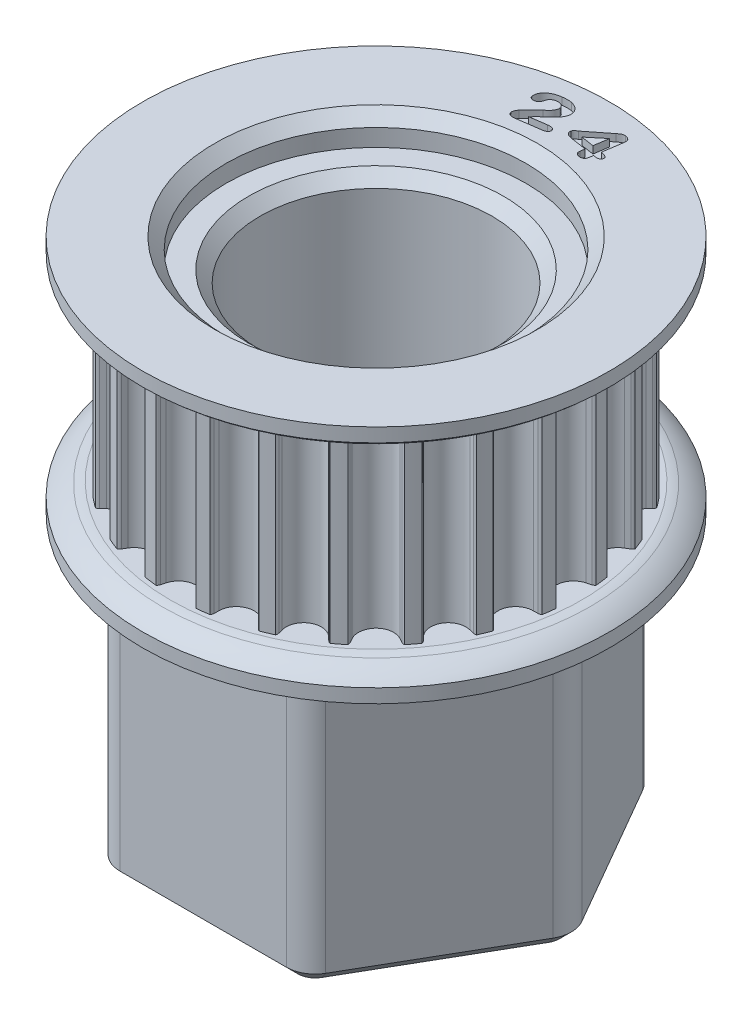
SolidWorks part; units mm, degrees
other "DetailItem2"
material "Markforged"
ref_plane "Front Plane" through (0, 0, 0) normal (0, 0, 1) x (1, 0, 0)
ref_plane "Top Plane" through (0, 0, 0) normal (0, 1, 0) x (1, 0, 0)
ref_plane "Right Plane" through (0, 0, 0) normal (1, 0, 0) x (0, 0, -1)
ref_axis "Centerline" through (0, 8.7312, 0) along (0, -1, 0)
sketch "Sketch1" plane through (0, 0, 0) normal (0, 1, 0) x (1, 0, 0)
  circle A0 centre (0, 0) radius 11.0782
  dimension "OuterDiameter" = 22.1563
extrude "ToothOD" add sketch "Sketch1" along normal mid plane 10.16
sketch "Sketch2" plane through (0, 0, 0) normal (0, 1, 0) x (1, 0, 0)
  line L0 (0, 9.9098) -> (50000, 9.9098) construction
  line L1 (0, 11.0782) -> (50000, 11.0782) construction
  line L2 (0, 0) -> (0, 50000) construction
  arc A0 (-0.937, 10.6282) -> (0, 9.9098) centre (0, 10.88) ccw
  arc A1 (-1.1005, 11.0234) -> (1.1005, 11.0234) centre (0, 0) cw
  circle A2 centre (0, 0) radius 11.0782 construction
  arc A3 (-0.937, 10.6282) -> (-1.0078, 10.88) centre (-11.9754, 7.6618) ccw
  arc A4 (-1.0078, 10.88) -> (-1.1005, 11.0234) centre (-1.2954, 10.7956) ccw
  circle A5 centre (0, 0) radius 11.0782 construction
  arc A6 (0.937, 10.6282) -> (1.0078, 10.88) centre (11.9754, 7.6618) cw
  arc A7 (1.0078, 10.88) -> (1.1005, 11.0234) centre (1.2954, 10.7956) cw
  arc A8 (0, 9.9098) -> (0.937, 10.6282) centre (0, 10.88) ccw
  dimension "D1" = 1.9406
  dimension "D3" = 22.86
  dimension "D4" = 0.5994
  dimension "D2" = 1.1684
  dimension "D5" = 1.2954
extrude "ToothProfile" cut sketch "Sketch2" against normal through all both and the other way through all
pattern_circular "ToothPattern" count 24 over 360 about axis through (0, 5.08, 0) along (0, -1, 0) of "ToothProfile"
sketch "Sketch4" plane through (0, 0, 0) normal (0, 0, 1) x (1, 0, 0)
  line L0 (0, -5.08) -> (11.3322, -5.08)
  line L1 (0, -6.604) -> (12.8562, -6.604)
  line L2 (0, -6.604) -> (0, -5.08)
  line L3 (12.8562, -6.604) -> (12.8562, -5.842)
  line L4 (0, 0) -> (50000, 0) construction
  line L5 (12.8562, 6.604) -> (12.8562, 5.842)
  line L6 (0, 6.604) -> (0, 5.08)
  line L7 (0, 6.604) -> (12.8562, 6.604)
  line L8 (0, 5.08) -> (11.3322, 5.08)
  arc A0 (11.3322, -5.08) -> (11.7872, -5.1726) centre (11.0525, -7.618) cw
  arc A2 (11.7872, -5.1726) -> (12.8562, -5.842) centre (10.6547, -8.1694) cw
  arc A3 (11.7872, 5.1726) -> (12.8562, 5.842) centre (10.6547, 8.1694) ccw
  arc A4 (11.3322, 5.08) -> (11.7872, 5.1726) centre (11.0525, 7.618) ccw
  dimension "D5" = 2.5534
  dimension "D6" = 3.2036
  dimension "FlangeID" = 11.3322
  dimension "FlangeOD" = 12.8562
  dimension "D1" = 1.524
  dimension "D2" = 0.762
  dimension "D3" = 5.08
  dimension "D4" = 13.208
  dimension "D7" = 0.762
  dimension "D8" = 0.6694
  dimension "D10" = 1.0689
revolve "Flange" add sketch "Sketch4" angle 360 about axis through (0, 8.7312, 0) along (0, -1, 0)
sketch "Sketch6" plane through (0, 0, 0) normal (0, 0, 1) x (1, 0, 0)
  line L0 (0, -6.604) -> (0, -7.9375) construction
  line L1 (-12.8562, -6.604) -> (12.8562, -6.604) construction
  line L2 (0, -7.9375) -> (8.2931, -7.9375) construction
  line L3 (8.2931, -7.9375) -> (8.2931, -6.604) construction
  line L4 (8.2931, -6.604) -> (0, -6.604) construction
  line L5 (0, 0) -> (50000, 0) construction
  line L6 (8.2931, 6.604) -> (0, 6.604)
  line L7 (8.2931, 7.9375) -> (8.2931, 6.604)
  line L8 (0, 7.9375) -> (8.2931, 7.9375)
  line L9 (0, 6.604) -> (0, 7.9375)
  line L11 (36.0254, 12.0878) -> (29.4657, 15.4613) construction
  line L12 (29.4657, 15.4613) -> (23.2643, 11.4672) construction
  line L13 (23.2643, 11.4672) -> (23.6226, 4.0996) construction
  line L14 (23.6226, 4.0996) -> (30.1823, 0.7261) construction
  line L15 (30.1823, 0.7261) -> (36.3837, 4.7202) construction
  line L16 (36.3837, 4.7202) -> (36.0254, 12.0878) construction
  circle A0 centre (29.824, 8.0937) radius 6.3881 construction
  circle A1 centre (29.824, 8.0937) radius 8.2931 construction
  dimension "D2" = 12.7762
  dimension "D1" = 15.875
  dimension "D4" = 8.2931
  dimension "D3" = 1.905
  dimension "D5" = 1.3335
revolve "TopBearingBoss" [suppressed] add sketch "Sketch6" angle 360 about axis through (0, 8.7312, 0) along (0, -1, 0)
mirror "BottomBearingBoss" [suppressed] about plane through (0, 0, 0) normal (0, 1, 0)
sketch "Sketch7" plane through (0, 0, 0) normal (0, -1, 0) x (1, 0, 0)
  line L1 (3.6882, 6.3881) -> (-3.6882, 6.3881) construction
  line L2 (-3.6882, 6.3881) -> (-7.3763, 0) construction
  line L3 (-7.3763, 0) -> (-3.6882, -6.3881) construction
  line L4 (-3.6882, -6.3881) -> (3.6882, -6.3881) construction
  line L5 (3.6882, -6.3881) -> (7.3763, 0) construction
  line L6 (7.3763, 0) -> (3.6882, 6.3881) construction
  circle A0 centre (0, 0) radius 6.3881
  dimension "HexBoreDi," = 12.7762
extrude "Bore" cut sketch "Sketch7" against normal through all both and the other way through all
sketch "Sketch9" plane through (0, 6.604, 0) normal (0, 1, 0) x (1, 0, 0)
  arc A0 (-6.4927, -6.4927) -> (6.4927, -6.4927) centre (0, 0) cw construction
  text T0 "24" font "Arial Rounded MT Bold" height 4.572
  point P3 (0, 9.1821)
  dimension "D1" = 9.1821
  dimension "D2" = 270
extrude "Large Tooth Count" [suppressed] cut sketch "Sketch9" against normal blind 0.4 and the other way through all
sketch "Sketch11" plane through (0, 6.604, 0) normal (0, 1, 0) x (1, 0, 0)
  arc A0 (-6.8456, -6.8456) -> (6.8456, -6.8456) centre (0, 0) cw construction
  circle A1 centre (0, 0) radius 12.8562 construction
  text T0 "<b>24</b>" font "Arial Rounded MT Bold" height 2.286
  point P6 (0, 9.6812)
  dimension "D1" = 3.175
  dimension "D3" = 270
extrude "Small Tooth Count" cut sketch "Sketch11" against normal blind 0.4 and the other way through all
sketch "Sketch12" plane through (0, -6.604, 0) normal (0, -1, 0) x (1, 0, 0)
  line L1 (5.4993, -9.525) -> (10.9985, 0)
  line L2 (10.9985, 0) -> (5.4993, 9.525)
  line L3 (5.4993, 9.525) -> (-5.4993, 9.525)
  line L4 (-5.4993, 9.525) -> (-10.9985, 0)
  line L5 (-10.9985, 0) -> (-5.4993, -9.525)
  line L6 (-5.4993, -9.525) -> (5.4993, -9.525)
  circle A0 centre (0, 0) radius 6.3881 construction
  circle A1 centre (0, 0) radius 6.3881
  circle A2 centre (0, 0) radius 9.525 construction
  dimension "D1" = 19.05
extrude "Boss-Extrude1" add sketch "Sketch12" along normal blind 15.24
sketch "Sketch27" plane through (0, 6.604, 0) normal (0, 1, 0) x (1, 0, 0)
  circle A0 centre (0, 0) radius 8.255
  dimension "D1" = 16.51
extrude "Cut-Extrude1" cut sketch "Sketch27" against normal blind 1.5875
fillet "Fillet1" radius 1.5875 6 edges at (-5.4993, -14.224, 9.525) (5.4993, -14.224, 9.525) (10.9985, -14.224, 0) (5.4993, -14.224, -9.525) (-10.9985, -14.224, 0) (-5.4993, -14.224, -9.525)
sketch "Sketch25" plane through (0, -6.604, 0) normal (0, -1, 0) x (1, 0, 0)
  line L6 (-4.5827, -9.525) -> (4.5827, -9.525)
  line L7 (-10.5403, -0.7937) -> (-5.9575, -8.7313)
  line L8 (-5.9575, 8.7312) -> (-10.5403, 0.7938)
  line L9 (4.5827, 9.525) -> (-4.5827, 9.525)
  line L10 (10.5403, 0.7938) -> (5.9575, 8.7312)
  line L11 (5.9575, -8.7312) -> (10.5403, -0.7937)
  line L12 (-4.5827, -9.525) -> (4.5827, -9.525)
  line L13 (-10.5403, -0.7937) -> (-5.9575, -8.7313)
  line L14 (-5.9575, 8.7312) -> (-10.5403, 0.7938)
  line L15 (4.5827, 9.525) -> (-4.5827, 9.525)
  line L16 (10.5403, 0.7938) -> (5.9575, 8.7312)
  line L17 (5.9575, -8.7312) -> (10.5403, -0.7937)
  arc A6 (-5.9575, -8.7313) -> (-4.5827, -9.525) centre (-4.5827, -7.9375) ccw
  arc A7 (-10.5403, 0.7938) -> (-10.5403, -0.7937) centre (-9.1654, 0) ccw
  arc A8 (-4.5827, 9.525) -> (-5.9575, 8.7312) centre (-4.5827, 7.9375) ccw
  arc A9 (5.9575, 8.7312) -> (4.5827, 9.525) centre (4.5827, 7.9375) ccw
  arc A10 (10.5403, -0.7937) -> (10.5403, 0.7938) centre (9.1654, 0) ccw
  arc A11 (4.5827, -9.525) -> (5.9575, -8.7312) centre (4.5827, -7.9375) ccw
  arc A12 (-5.9575, -8.7313) -> (-4.5827, -9.525) centre (-4.5827, -7.9375) ccw
  arc A13 (-10.5403, 0.7938) -> (-10.5403, -0.7937) centre (-9.1654, 0) ccw
  arc A14 (-4.5827, 9.525) -> (-5.9575, 8.7312) centre (-4.5827, 7.9375) ccw
  arc A15 (5.9575, 8.7312) -> (4.5827, 9.525) centre (4.5827, 7.9375) ccw
  arc A16 (10.5403, -0.7937) -> (10.5403, 0.7938) centre (9.1654, 0) ccw
  arc A17 (4.5827, -9.525) -> (5.9575, -8.7312) centre (4.5827, -7.9375) ccw
  dimension "D1" = 0
sweep "Cut-Sweep1" cut path "Sketch25" circular profile diameter 0.635 parameters "D3"=0.635
fillet "Fillet2" radius 1.27 24 edges at (-5.5352, -6.604, 9.5873) (0, -6.604, 9.8425) (5.5352, -6.604, 9.5873) (8.5239, -6.604, 4.9213) (11.0704, -6.604, 0) (8.5239, -6.604, -4.9212) (5.5352, -6.604, -9.5873) (0, -6.604, -9.8425) (-5.5352, -6.604, -9.5873) (-8.5239, -6.604, -4.9213) (-11.0704, -6.604, 0) (-10.7529, -6.9215, 0) (-8.2489, -6.9215, -4.7625) (-5.3765, -6.9215, -9.3123) (0, -6.9215, -9.525) (5.3765, -6.9215, -9.3123) (8.2489, -6.9215, -4.7625) (10.7529, -6.9215, 0) (8.2489, -6.9215, 4.7625) (5.3765, -6.9215, 9.3123) (0, -6.9215, 9.525) (-5.3765, -6.9215, 9.3123) (-8.5239, -6.604, 4.9212) (-8.2489, -6.9215, 4.7625)
chamfer "Chamfer1" distance 0.635 angle 45 3 edges at (0, -21.844, -6.3881) (0, 6.604, 8.255) (0, 5.0165, 6.3881)
chamfer "Chamfer2" distance 0.635 angle 45 12 edges at (0, -21.844, -9.525) (5.3765, -21.844, -9.3123) (-5.3765, -21.844, -9.3123) (8.2489, -21.844, -4.7625) (-8.2489, -21.844, -4.7625) (10.7529, -21.844, 0) (-10.7529, -21.844, 0) (8.2489, -21.844, 4.7625) (-8.2489, -21.844, 4.7625) (5.3765, -21.844, 9.3123) (-5.3765, -21.844, 9.3123) (0, -21.844, 9.525)
equation "\"OuterDiameter@Sketch1\"= \"OD\""
equation "\"Teeth\"= \"No_Teeth\""
equation "\"PD\"= \"No_Teeth\" * 3mm / pi"
equation "\"OD\"= \"PD\" - .030"
equation "\"ToothCount@ToothPattern\" = \"Teeth\""
equation "\"Angle\"= 360 / \"Teeth\""
equation "\"AngleSpacing@ToothPattern\" = \"Angle\""
equation "\"FlangeID@Sketch4\"=\"OD\"/2+.01"
equation "\"FlangeOD@Sketch4\"=\"PD\"/2+.055"
equation "\"D3@Sketch4\"=\"Tooth_Face_Length\"/2"
equation "\"Bearing_Feature\"= \"Bearing_Boss\""
equation "\"TopBearingBoss\" = IIF ( \"Bearing_Feature\" > 0 , \"unsuppressed\" , \"suppressed\" )"
equation "\"HexBore\"= \"Hex_Bore\" + \"Print_Tolerance\""
equation "\"HexBoreDi,@Sketch7\"= \"HexBore\""
equation "\"D2@Sketch6\"=\"HexBore\""
equation "\"D4@Sketch6\"=\"HexBore\"/2+.075"
equation "\"Large Tooth Count\" = iif ( \"No_Teeth\" < \"TextTooth\" , \"suppressed\" , \"unsuppressed\" )"
equation "\"Small Tooth Count\"= iif ( \"No_Teeth\" < \"TextTooth\" , \"unsuppressed\" , \"suppressed\" )"
equation "\"BottomBearingBoss\" = iif ( \"Bearing_Feature\" > 1 , \"unsuppressed\" , \"suppressed\" )"
equation "\"ToothFaceLength@ToothOD\" = \"Tooth_Face_Length\""
equation "\"D4@Sketch4\" = \"Width_No_BearingBoss\""
equation "\"D1@Sketch9\"=\"HexBore\"/2+.11"
equation "\"TextTooth\"= iif ( \"Hex_Bore\" <= .380 , 23 , iif ( \"Hex_Bore\" <= .505 , 25 , 16 ) )"
equation "\"D1@Sketch6\"=\"Overall_Width\""
